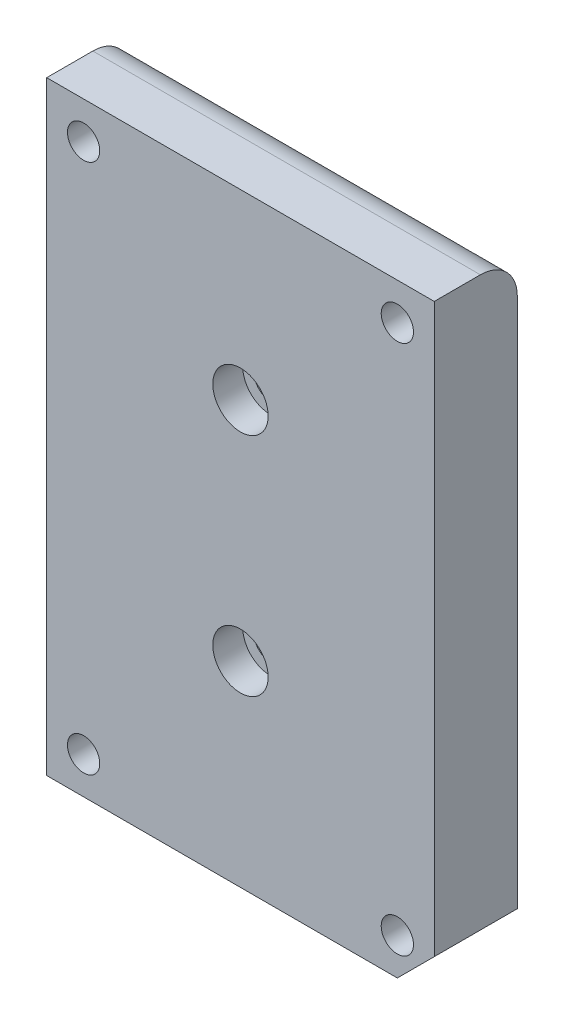
SolidWorks part; units mm, degrees
ref_plane "Front Plane" through (0, 0, 0) normal (0, 0, 1) x (1, 0, 0)
ref_plane "Top Plane" through (0, 0, 0) normal (0, 1, 0) x (1, 0, 0)
ref_plane "Right Plane" through (0, 0, 0) normal (1, 0, 0) x (0, 0, -1)
sketch "Sketch1" plane through (0, 0, 0) normal (0, 0, 1) x (1, 0, 0)
  line L1 (0, 0) -> (42, 0)
  line L2 (0, 0) -> (0, 65.5)
  line L3 (0, 65.5) -> (42, 65.5)
  line L4 (42, 0) -> (42, 65.5)
  dimension "D1" = 42
  dimension "D2" = 65.5
extrude "Boss-Extrude1" add sketch "Sketch1" along normal blind 9
sketch "Sketch2" plane through (0, 0, 0) normal (0, 0, -1) x (-1, 0, 0)
  line L0 (-42, 32.75) -> (0, 32.75) construction
  line L1 (-42, 0) -> (-42, 65.5) construction
  line L2 (0, 65.5) -> (0, 0) construction
  line L3 (-42, 45.75) -> (0, 45.75) construction
  line L4 (-21, 45.75) -> (-21, 21.25) construction
  line L5 (-25.5, 21.25) -> (-25.5, 35.0846)
  line L6 (-16.5, 21.25) -> (-16.5, 35.0846)
  arc A0 (-14.5556, 41.0098) -> (-27.4444, 41.0098) centre (-21, 45.75) ccw
  arc A1 (-25.5, 21.25) -> (-16.5, 21.25) centre (-21, 21.25) ccw
  arc A2 (-16.5, 35.0846) -> (-14.5556, 41.0098) centre (-6.5, 35.0846) cw
  arc A3 (-25.5, 35.0846) -> (-27.4444, 41.0098) centre (-35.5, 35.0846) ccw
  point P11 (-21, 45.75)
  dimension "D2" = 16
  dimension "D3" = 9
  dimension "D5" = 10
  dimension "D4" = 24.5
  dimension "D1" = 13
extrude "Cut-Extrude2" cut sketch "Sketch2" against normal blind 4.5
sketch "Sketch3" plane through (0, 0, 4.5) normal (0, 0, -1) x (-1, 0, 0)
  line L0 (-21, 45.75) -> (-21, 25.25) construction
  line L1 (-21, 25.25) -> (-21, 21.25) construction
  line L2 (-24, 21.25) -> (-24, 25.25)
  line L3 (-18, 25.25) -> (-18, 21.25)
  arc A0 (-18, 25.25) -> (-24, 25.25) centre (-21, 25.25) ccw
  arc A1 (-24, 21.25) -> (-18, 21.25) centre (-21, 21.25) ccw
  circle A2 centre (-21, 25.25) radius 1.75
  circle A3 centre (-21, 21.25) radius 1.75
  circle A4 centre (-21, 45.75) radius 1.75
  dimension "D2" = 6
  dimension "D4" = 3.5
  dimension "D5" = 3.5
  dimension "D1" = 20.5
  dimension "D3" = 4
extrude "Cut-Extrude5" cut sketch "Sketch3" against normal through all contours A3 | A4 region at (21, 21.25, 4.5) region at (21, 45.75, 4.5)
sketch "Sketch5" plane through (0, 0, 9) normal (0, 0, 1) x (1, 0, 0)
  circle A0 centre (21, 21.25) radius 3
  circle A1 centre (21, 45.75) radius 3
  dimension "D1" = 6
extrude "Cut-Extrude6" cut sketch "Sketch5" against normal blind 3.25
fillet "Fillet1" radius 4 2 edges at (21, 0, 0) (21, 65.5, 0)
sketch "Sketch6" plane through (0, 0, 0) normal (0, 0, -1) x (-1, 0, 0)
  line L0 (-4, 61.5) -> (-4, 4) construction
  line L1 (-42, 65.5) -> (0, 65.5) construction
  line L2 (-42, 65.5) -> (-42, 0) construction
  line L3 (-42, 0) -> (0, 0) construction
  line L4 (0, 65.5) -> (0, 0) construction
  line L5 (-38, 4) -> (-4, 4) construction
  line L6 (-38, 61.5) -> (-38, 4) construction
  line L7 (-38, 61.5) -> (-4, 61.5) construction
  circle A0 centre (-38, 61.5) radius 1.75
  circle A1 centre (-4, 61.5) radius 1.75
  circle A2 centre (-4, 4) radius 1.75
  circle A3 centre (-38, 4) radius 1.75
  line M16 (-42, 4) -> (0, 4)
  dimension "D2" = 3.5
  dimension "D1" = 4
extrude "Cut-Extrude7" cut sketch "Sketch6" against normal through all contours A2 M16 | A2 M16 | A3 M16 | A3 M16 | A0 | A1 region at (4, 4.7427, 0) region at (38, 3.2573, 0) region at (38, 4.7427, 0) region at (4, 3.2573, 0)
sketch "Sketch7" plane through (0, 0, 0) normal (0, 0, -1) x (-1, 0, 0)
  circle A0 centre (-38, 61.5) radius 3
  circle A1 centre (-4, 61.5) radius 3
  circle A2 centre (-4, 4) radius 3
  circle A3 centre (-38, 4) radius 3
  dimension "D1" = 6
extrude "Cut-Extrude8" cut sketch "Sketch7" against normal blind 3
sketch "Sketch8" plane through (0, 0, 9) normal (0, 0, 1) x (1, 0, 0)
  line L0 (42, 0) -> (38, 0)
  line L1 (0, 0) -> (42, 0) construction
  line L2 (38, 0) -> (42, 4)
  line L3 (42, 0) -> (42, 65.5) construction
  line L4 (42, 4) -> (42, 0)
  dimension "D1" = 4
extrude "Cut-Extrude9" cut sketch "Sketch8" against normal through all
fillet "Fillet3" radius 0.5 2 edges at (39.2929, 1.2929, 2.0276) (40.7071, 2.7071, 1.6074)
equation "\"`\"=10"
